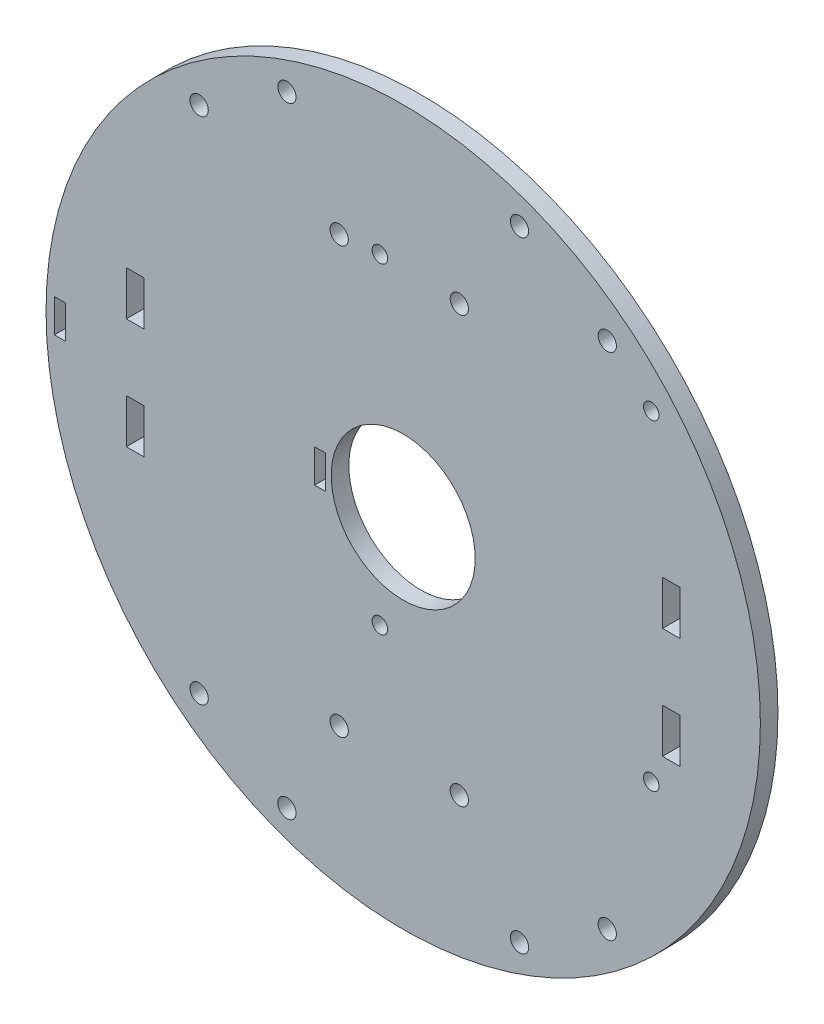
SolidWorks part; units mm, degrees
material "Acrylic (Medium-high impact)"
ref_plane "Front Plane" through (0, 0, 0) normal (0, 0, 1) x (1, 0, 0)
ref_plane "Top Plane" through (0, 0, 0) normal (0, 1, 0) x (1, 0, 0)
ref_plane "Right Plane" through (0, 0, 0) normal (1, 0, 0) x (0, 0, -1)
sketch "Sketch1" plane through (0, 0, 0) normal (0, 0, 1) x (-1, 0, 0)
  line L0 (18.6668, -38.6336) -> (-30.3332, -38.6336) construction
  line L1 (18.6668, 19.3664) -> (-30.3332, 19.3664) construction
  line L2 (14.4554, 64.8664) -> (14.4554, -64.1336) construction
  line L4 (18.6668, -42.1336) -> (-30.3332, -42.1336) construction
  line L5 (78.9554, 0.3664) -> (-50.0446, 0.3664) construction
  line L6 (28.4554, 3.3664) -> (30.4554, 3.3664)
  line L7 (28.4554, 3.3664) -> (28.4554, -2.6336)
  line L8 (28.4554, -2.6336) -> (30.4554, -2.6336)
  line L9 (30.4554, 3.3664) -> (30.4554, -2.6336)
  line L10 (18.6668, -42.1336) -> (18.6668, 42.8664) construction
  line L11 (18.6668, 42.8664) -> (-30.3332, 42.8664) construction
  line L12 (75.4554, 3.3664) -> (77.4554, 3.3664)
  line L13 (75.4554, 3.3664) -> (75.4554, -2.6336)
  line L14 (75.4554, -2.6336) -> (77.4554, -2.6336)
  line L15 (77.4554, 3.3664) -> (77.4554, -2.6336)
  line L16 (-30.3332, -42.1336) -> (-30.3332, 42.8664) construction
  circle A1 centre (14.4554, 0.3664) radius 64.5
  circle A5 centre (26.0186, -38.0586) radius 1.65
  circle A7 centre (4.3186, -38.0586) radius 1.65
  circle A8 centre (26.0186, 38.7914) radius 1.65
  circle A9 centre (4.3186, 38.7914) radius 1.65
  circle A10 centre (14.4554, 0.3664) radius 13
  circle A15 centre (-6.5446, 56.3664) radius 1.65
  circle A16 centre (-22.3949, 46.3664) radius 1.65
  circle A17 centre (35.4554, 56.3664) radius 1.65
  circle A18 centre (51.3057, 46.3664) radius 1.65
  circle A19 centre (51.3057, -45.6336) radius 1.65
  circle A20 centre (35.4554, -55.6336) radius 1.65
  circle A21 centre (-6.5446, -55.6336) radius 1.65
  circle A22 centre (-22.3949, -45.6336) radius 1.65
  circle A23 centre (18.6668, -38.6336) radius 1.4
  circle A24 centre (-30.3332, -38.6336) radius 1.4
  circle A25 centre (18.6668, 19.3664) radius 1.4
  circle A26 centre (-30.3332, 19.3664) radius 1.4
  dimension "D3" = 23.5
  dimension "D4" = 38.425
  dimension "D9" = 26
  dimension "D10" = 3.3
  dimension "D11" = 56
  dimension "D12" = 46
  dimension "D13" = 3.5
  dimension "D20" = 129
  dimension "D16" = 44.7886
  dimension "D5" = 49
  dimension "D15" = 2.8
  dimension "D6" = 21.7
  dimension "D7" = 85
  dimension "D8" = 42.5
  dimension "D14" = 21
  dimension "D17" = 2
  dimension "D18" = 6
  dimension "D19" = 3
  dimension "D21" = 45
  dimension "D22" = 14
extrude "Boss-Extrude2" add sketch "Sketch1" along normal blind 3.175
sketch "Sketch2" plane through (0, 0, 3.175) normal (0, 0, 1) x (1, 0, 0)
  line L0 (-78.9554, -0.3664) -> (50.0446, -0.3664) construction
  line L1 (35.5446, -14.3664) -> (32.3696, -14.3664)
  line L2 (35.5446, -14.3664) -> (35.5446, -6.3664)
  line L3 (35.5446, -6.3664) -> (32.3696, -6.3664)
  line L4 (32.3696, -14.3664) -> (32.3696, -6.3664)
  line L5 (35.5446, -14.3664) -> (32.3696, -6.3664) construction
  line L6 (35.5446, -6.3664) -> (32.3696, -14.3664) construction
  line L11 (50.0446, -0.3664) -> (-78.9554, -0.3664) construction
  line L12 (-14.4554, -64.8664) -> (-14.4554, 64.1336) construction
  line L13 (35.5446, 5.6336) -> (32.3696, 13.6336) construction
  line L14 (35.5446, 13.6336) -> (32.3696, 5.6336) construction
  line L15 (32.3696, 13.6336) -> (32.3696, 5.6336)
  line L16 (35.5446, 5.6336) -> (32.3696, 5.6336)
  line L17 (35.5446, 13.6336) -> (35.5446, 5.6336)
  line L18 (35.5446, 13.6336) -> (32.3696, 13.6336)
  line L19 (-64.4554, 13.6336) -> (-61.2804, 5.6336) construction
  line L20 (-64.4554, 5.6336) -> (-61.2804, 13.6336) construction
  line L21 (-64.4554, -6.3664) -> (-61.2804, -14.3664) construction
  line L22 (-64.4554, -14.3664) -> (-61.2804, -6.3664) construction
  line L23 (-64.4554, 13.6336) -> (-61.2804, 13.6336)
  line L24 (-64.4554, 13.6336) -> (-64.4554, 5.6336)
  line L25 (-64.4554, 5.6336) -> (-61.2804, 5.6336)
  line L26 (-61.2804, 13.6336) -> (-61.2804, 5.6336)
  line L27 (-61.2804, -14.3664) -> (-61.2804, -6.3664)
  line L28 (-64.4554, -6.3664) -> (-61.2804, -6.3664)
  line L29 (-64.4554, -14.3664) -> (-64.4554, -6.3664)
  line L30 (-64.4554, -14.3664) -> (-61.2804, -14.3664)
  circle A0 centre (-14.4554, -0.3664) radius 64.5 construction
  point P0 (33.9571, -10.3664)
  point P21 (33.9571, 9.6336)
  point P30 (-62.8679, 9.6336)
  point P31 (-62.8679, -10.3664)
  dimension "D1" = 8
  dimension "D2" = 3.175
  dimension "D3" = 6
  dimension "D4" = 50
extrude "Cut-Extrude1" cut sketch "Sketch2" against normal through all
